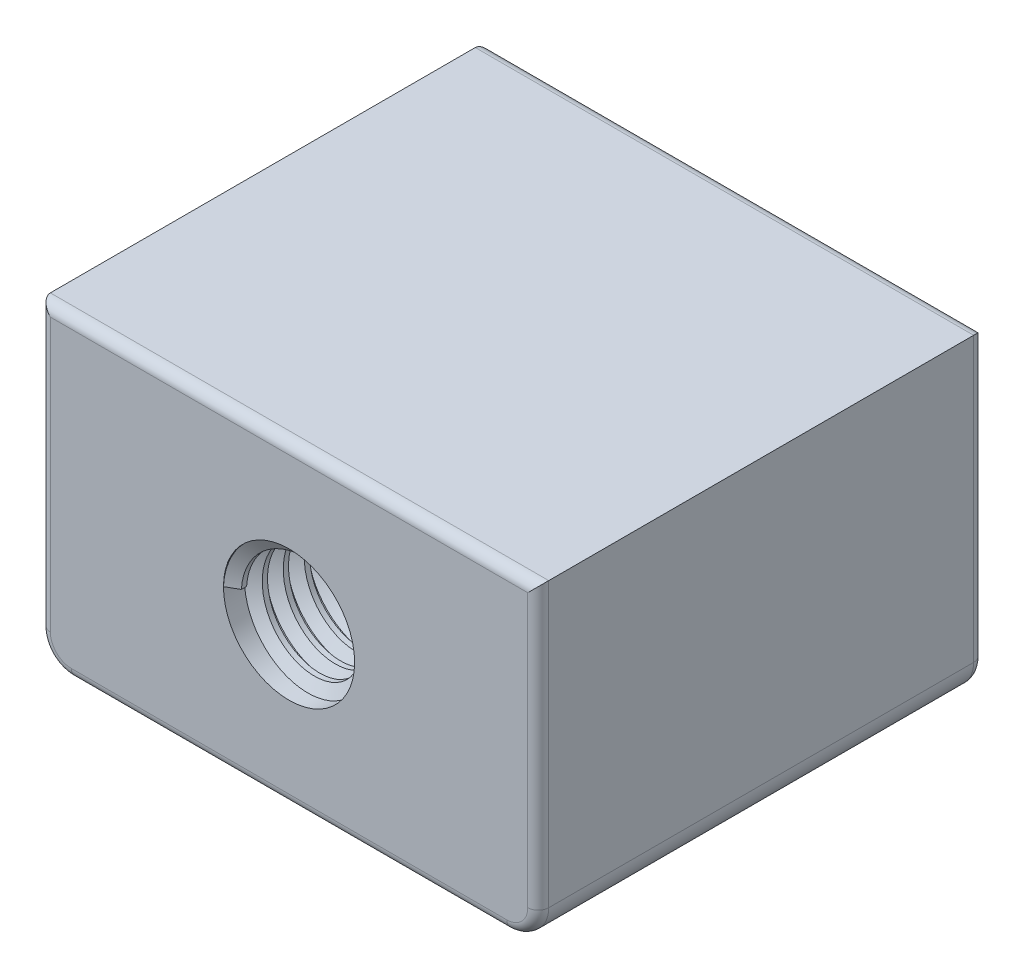
SolidWorks part; units mm, degrees
ref_plane "Front Plane" through (0, 0, 0) normal (0, 0, 1) x (1, 0, 0)
ref_plane "Top Plane" through (0, 0, 0) normal (0, 1, 0) x (1, 0, 0)
ref_plane "Right Plane" through (0, 0, 0) normal (1, 0, 0) x (0, 0, -1)
sketch "Sketch1" plane through (0, 0, 0) normal (0, 0, 1) x (1, 0, 0)
  line L1 (-9.5, 6) -> (9.5, 6)
  line L2 (-9.5, 6) -> (-9.5, -6)
  line L3 (-9.5, -6) -> (9.5, -6)
  line L4 (9.5, 6) -> (9.5, -6)
  line L5 (-9.5, 6) -> (9.5, -6) construction
  line L6 (-9.5, -6) -> (9.5, 6) construction
  point P0 (0, 0)
  dimension "D1" = 19
  dimension "D2" = 12
extrude "Boss-Extrude1" add sketch "Sketch1" along normal blind 17
fillet "Fillet1" radius 1.2 2 edges at (-9.5, -6, 8.5) (9.5, -6, 8.5)
sketch "Sketch2" plane through (0, 0, 17) normal (0, 0, 1) x (1, 0, 0)
  circle A0 centre (0, 0) radius 2.5
  dimension "D1" = 5
extrude "Cut-Extrude1" cut sketch "Sketch2" against normal through all
thread "Thread1" pitch 0.8 method extrude profile "Thread Profile1" start angle 0, offset 0, length 7, pitch 0.8, diameter 5
ref_plane "Plane1" through (-2.5, 0, 17) normal (0, -1, 0) x (-1, 0, 0)
sketch "Thread Profile1" plane through (-2.5, 0, 17) normal (0, -1, 0) x (-1, 0, 0)
  line L0 (0, 0) -> (0, 0.8) construction
  line L11 (0, 0) -> (0, 0.7)
  line L12 (0, 0.7) -> (-0.433, 0.45)
  line L13 (-0.433, 0.45) -> (-0.433, 0.25)
  line L15 (-0.433, 0.25) -> (0, 0)
  line L17 (-0.433, 0.35) -> (0, 0.35) construction
  point P2 (0, 0)
  dimension "Pitch" = 0.8
  dimension "Profile_Angle" = 60
  dimension "Profile_Land" = 0.2
  dimension "Profile_Height" = 0.433
fillet "Fillet2" radius 0.4 13 edges at (9.5, 0.6, 17) (9.1485, -5.6485, 17) (0, -6, 17) (-9.1485, -5.6485, 17) (9.1485, -5.6485, 0) (9.5, 0.6, 0) (0, 6, 0) (-9.5, 0.6, 0) (-9.1485, -5.6485, 0) (0, -6, 0) (2.5, 0, 0) (-9.5, 0.6, 17) (0, 6, 17)
